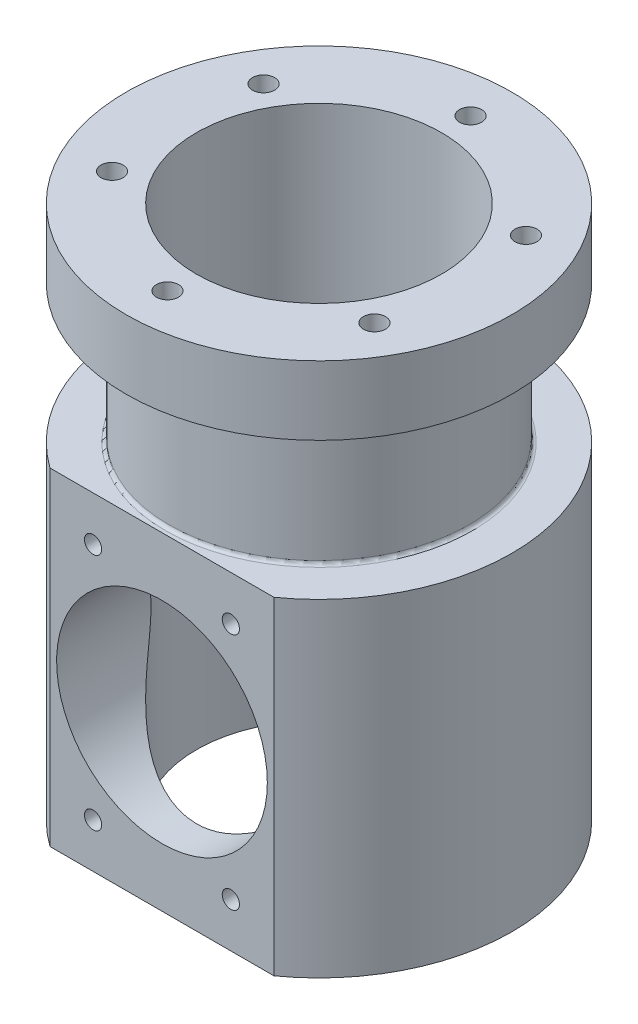
SolidWorks part; units mm, degrees
material "1060 Alloy"
ref_plane "Front Plane" through (0, 0, 0) normal (0, 0, 1) x (1, 0, 0)
ref_plane "Top Plane" through (0, 0, 0) normal (0, 1, 0) x (1, 0, 0)
ref_plane "Right Plane" through (0, 0, 0) normal (1, 0, 0) x (0, 0, -1)
sketch "Sketch1" plane through (0, 0, 0) normal (0, 0, 1) x (1, 0, 0)
  circle A0 centre (0, 0) radius 6.65
  circle A1 centre (0, 0) radius 7.15
  dimension "D1" = 13.3
  dimension "D2" = 14.3
extrude "Boss-Extrude1" add sketch "Sketch1" along normal blind 15
sketch "Sketch2" plane through (0, 0, 0) normal (0, 1, 0) x (1, 0, 0)
  circle A0 centre (0, 8.9) radius 8.9
  circle A1 centre (0, 8.9) radius 14
  dimension "D1" = 17.8
  dimension "D2" = 28
extrude "Boss-Extrude2" add sketch "Sketch2" along normal blind 26.9 and the other way blind 11.9
sketch "Sketch50" plane through (0, 26.9, 0) normal (0, 1, 0) x (1, 0, 0)
  circle A0 centre (0, 8.9) radius 10.9
  circle A1 centre (0, 8.9) radius 14
  circle A2 centre (0, 8.9) radius 14 construction
  circle A3 centre (0, 8.9) radius 8.9 construction
  dimension "D1" = 0
  dimension "D2" = 2
extrude "Cut-Extrude12" cut sketch "Sketch50" against normal blind 10 from offset 5 offset against normal yes
ref_plane "Plane4" through (0, -11.9, 0) normal (0, -1, 0) x (-1, 0, 0)
sketch "Sketch30" plane through (0, 0, 15) normal (0, 0, 1) x (1, 0, 0)
  circle A0 centre (0, 0) radius 7.65
  dimension "D1" = 15.3
extrude "Cut-Extrude8" cut sketch "Sketch30" against normal blind 21.28 and the other way blind 10
sketch "Sketch31" plane through (0, 26.9, 0) normal (0, 1, 0) x (1, 0, 0)
  circle A0 centre (0, 8.9) radius 11
  dimension "D1" = 22
hole_wizard "Tap Drill for M2 Tap1" positions "Sketch46" profile "Sketch47" hole size "M2" standard "ISO"
sketch "Sketch46" plane through (0, 26.9, 0) normal (0, 1, 0) x (1, 0, 0)
  circle A0 centre (0, 8.9) radius 8.9 construction
  point P0 (0, -2.1)
  dimension "D1" = 11
sketch "Sketch47" plane through (0, 26.9, 2.1) normal (1, 0, 0) x (0, 0, 1)
  line L0 (0, 0) -> (0, 4.4807)
  line L1 (0, 4.4807) -> (0.8, 4)
  line L2 (0.8, 4) -> (0.8, 0)
  line L5 (0.8, 0) -> (0, 0)
  line L10 (0, 4.4807) -> (-0.8, 4) construction
  line L11 (0, -6.35) -> (0, 107.95) construction
  dimension "Hole Dia." = 1.6
  dimension "Hole Depth" = 4
  dimension "Drill Angle" = 118
pattern_circular "CirPattern3" count 6 over 360 about axis through (0, -11.9, -8.9) along (0, 1, 0) of "Tap Drill for M2 Tap1" reverse direction yes
ref_plane "Plane6" through (0, 7.5, 0) normal (0, 1, 0) x (1, 0, 0)
mirror "Mirror1" about plane through (0, 7.5, 0) normal (0, 1, 0) of "CirPattern3"
sketch "Sketch39" plane through (0, -11.9, 0) normal (0, -1, 0) x (1, 0, 0)
  circle A0 centre (0, 2.1) radius 0.8
  circle A1 centre (0, 2.1) radius 0.8 construction
  dimension "D1" = 0
  dimension "D2" = 0
extrude "Boss-Extrude3" add sketch "Sketch39" against normal up to surface (4.25 mm away) up to face at (0.3182, -7.6434, 2.2944)
sketch "Sketch38" plane through (0, 0, 0) normal (0, 0, 1) x (1, 0, 0)
  circle A0 centre (0, 0) radius 11.53
  dimension "D1" = 23.06
extrude "Cut-Extrude11" cut sketch "Sketch38" along normal blind 10 from offset 2.5 contours A0 region at (0, 0, 0)
sketch "Sketch51" plane through (0, 0, 0) normal (1, 0, 0) x (0, 0, -1)
  line L0 (-2.5, 8.1793) -> (-2.5, -8.1793) construction
  line L1 (-22.508, 14.8831) -> (-2.5, 14.8831)
  line L2 (-22.508, 14.8831) -> (-22.508, -17.6512)
  line L3 (-22.508, -17.6512) -> (-2.5, -17.6512)
  line L4 (-2.5, 14.8831) -> (-2.5, -17.6512)
  dimension "D1" = 0
extrude "Cut-Extrude13" cut sketch "Sketch51" against normal through all both and the other way through all
hole_wizard "Tap Drill for M1.6 Tap1" positions "Sketch48" profile "Sketch49" hole size "M1.6" standard "ISO"
sketch "Sketch48" plane through (0, 0, 2.5) normal (0, 0, 1) x (1, 0, 0)
  line L0 (-14.573, 0) -> (17.3722, 0) construction
  line L2 (-5, 8.6603) -> (0, 0) construction
  point P0 (-5, 8.6603)
  dimension "D1" = 10
  dimension "D2" = 60
sketch "Sketch49" plane through (-5, 8.6603, 2.5) normal (1, 0, 0) x (0, -1, 0)
  line L0 (0, 0) -> (0, 3.3755)
  line L1 (0, 3.3755) -> (0.625, 3)
  line L2 (0.625, 3) -> (0.625, 0)
  line L5 (0.625, 0) -> (0, 0)
  line L10 (0, 3.3755) -> (-0.625, 3) construction
  line L11 (0, -6.35) -> (0, 107.95) construction
  dimension "Hole Dia." = 1.25
  dimension "Hole Depth" = 3
  dimension "Drill Angle" = 118
pattern_circular "CirPattern4" count 6 over 360 about axis through (0, 0, 25) along (0, 0, -1) skipping 1, 4 of "Tap Drill for M1.6 Tap1" reverse direction yes
fillet "Fillet1" radius 0.25 2 edges at (0, 21.9, 2) (0, 11.9, 2)
